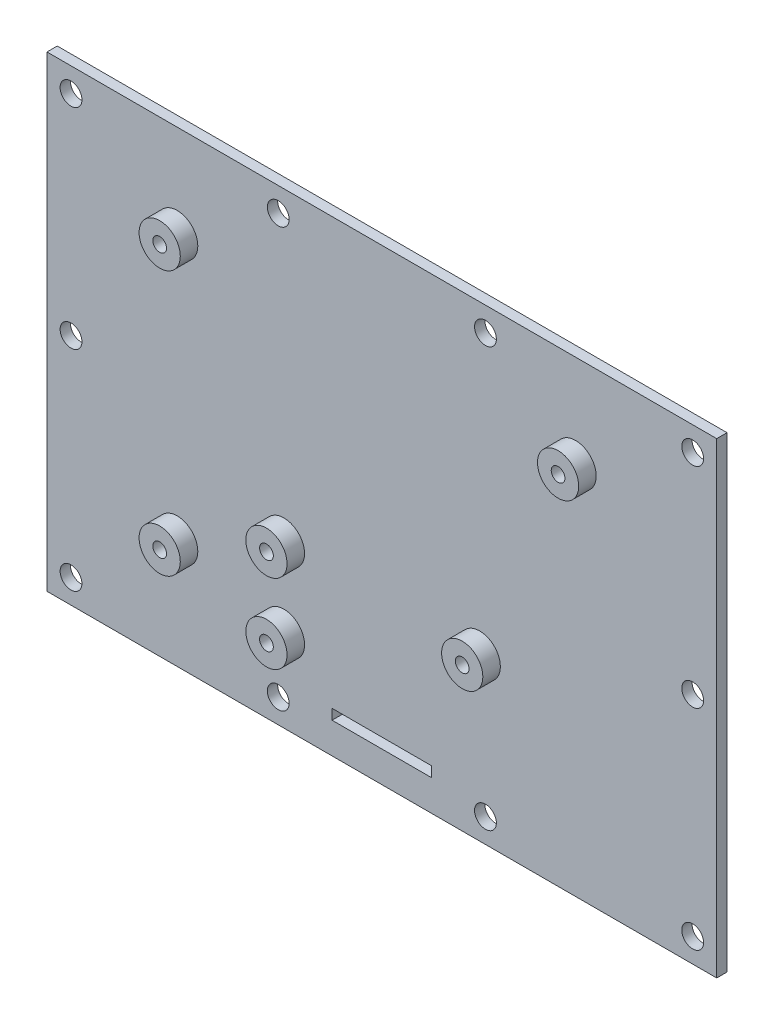
SolidWorks part; units mm, degrees
ref_plane "Front Plane" through (0, 0, 0) normal (0, 0, 1) x (1, 0, 0)
ref_plane "Top Plane" through (0, 0, 0) normal (0, 1, 0) x (1, 0, 0)
ref_plane "Right Plane" through (0, 0, 0) normal (1, 0, 0) x (0, 0, -1)
sketch "Sketch1" plane through (0, 0, 0) normal (0, 0, 1) x (1, 0, 0)
  line L1 (85.5, -56) -> (-85.5, -56)
  line L2 (85.5, -56) -> (85.5, 56)
  line L3 (85.5, 56) -> (-85.5, 56)
  line L4 (-85.5, -56) -> (-85.5, 56)
  line L5 (85.5, -56) -> (-85.5, 56) construction
  line L6 (85.5, 56) -> (-85.5, -56) construction
  line L11 (80, -45) -> (-80, -45)
  line L12 (80, -45) -> (80, 51)
  line L13 (80, 51) -> (-80, 51)
  line L14 (-80, -45) -> (-80, 51)
  line L15 (80, -45) -> (-80, 51) construction
  line L16 (80, 51) -> (-80, -45) construction
  line L17 (-14.5, -56) -> (14.5, -56)
  line L18 (-14.5, -56) -> (-14.5, -59)
  line L19 (-14.5, -59) -> (14.5, -59)
  line L20 (14.5, -56) -> (14.5, -59)
  line L21 (97.5, 68) -> (-97.5, 68)
  line L22 (97.5, 68) -> (97.5, -68)
  line L23 (97.5, -68) -> (-97.5, -68)
  line L24 (-97.5, 68) -> (-97.5, -68)
  line L25 (97.5, 68) -> (-97.5, -68) construction
  line L26 (97.5, -68) -> (-97.5, 68) construction
  point P0 (0, 0)
  point P6 (0, 0)
  point P7 (0, 3)
  point P16 (0, 0)
  dimension "D1" = 171
  dimension "D2" = 112
  dimension "D3" = 96
  dimension "D4" = 160
  dimension "D5" = 5
  dimension "D6" = 71
  dimension "D7" = 29
  dimension "D8" = 3
  dimension "D9" = 12
  dimension "D10" = 17.5
  dimension "D11" = 12
extrude "Boss-Extrude1" add sketch "Sketch1" against normal blind 1.5 contours L4 L1 L2 L3 L11 L14 L13 L12 | L21 L24 L23 L22 L1 L20 L19 L18 L4 L3 L2 | L14 L11 L12 L13 region at (50, -53.9559, 0) region at (0, 3, 0) region at (95.1226, 0, 0)
extrude "Boss-Extrude2" add sketch "Sketch1<3>" along normal blind 1.5 contours L21 L24 L23 L22 L1 L20 L19 L18 L4 L3 L2 | L4 L1 L2 L3 L11 L14 L13 L12 | L14 L11 L12 L13 region at (50, -53.9559, 0) region at (0, 3, 0) region at (95.1226, 0, 0)
sketch "Sketch1<3>" plane through (0, 0, 0) normal (0, 0, 1) x (1, 0, 0) same geometry as "Sketch1"
sketch "Sketch2" plane through (0, 0, 1.5) normal (0, 0, 1) x (1, 0, 0)
  line L0 (97.5, 68) -> (-97.5, 68) construction
  line L1 (90.5, -61) -> (-90.5, -61) construction
  line L2 (90.5, -61) -> (90.5, 61) construction
  line L3 (90.5, 61) -> (-90.5, 61) construction
  line L4 (-90.5, -61) -> (-90.5, 61) construction
  line L5 (90.5, -61) -> (-90.5, 61) construction
  line L6 (90.5, 61) -> (-90.5, -61) construction
  line L7 (-97.5, 68) -> (-97.5, -68) construction
  line L8 (-90.5, 61) -> (-30.1667, 61) construction
  line L9 (-30.1667, 61) -> (30.1667, 61) construction
  line L10 (30.1667, 61) -> (90.5, 61) construction
  circle A0 centre (-90.5, 61) radius 3.175
  circle A2 centre (90.5, 61) radius 3.175
  circle A3 centre (90.5, -61) radius 3.175
  circle A5 centre (-90.5, -61) radius 3.175
  circle A6 centre (-90.5, 0) radius 3.175
  circle A7 centre (30.1667, 61) radius 3.175
  circle A8 centre (90.5, 0) radius 3.175
  circle A9 centre (30.1667, -61) radius 3.175
  circle A10 centre (-30.1667, -61) radius 3.175
  circle A11 centre (-30.1667, 61) radius 3.175
  point P0 (0, 0)
  dimension "D1" = 6.35
  dimension "D2" = 7
  dimension "D3" = 7
extrude "Cut-Extrude1" cut sketch "Sketch2" against normal through all
sketch "Sketch3" plane through (0, 0, 1.5) normal (0, 0, 1) x (1, 0, 0)
  line L0 (-14.5, -59) -> (14.5, -59) construction
  line L1 (28.5, -44) -> (-28.5, -44) construction
  line L2 (28.5, -44) -> (28.5, -21) construction
  line L3 (28.5, -21) -> (-28.5, -21) construction
  line L4 (-28.5, -44) -> (-28.5, -21) construction
  line L5 (28.5, -44) -> (-28.5, -21) construction
  line L6 (28.5, -21) -> (-28.5, -44) construction
  line L11 (-12.1109, -44) -> (11.8889, -44) construction
  line L13 (-12.1109, -44) -> (-12.1109, -40) construction
  line L14 (-12.1109, -40) -> (11.8889, -40) construction
  line L15 (11.8889, -44) -> (11.8889, -40) construction
  line L16 (14.5, -56) -> (-14.5, -56) construction
  circle A0 centre (-28.5, -44) radius 6
  circle A1 centre (-28.5, -44) radius 2
  point P17 (-28.5, -21)
  point P18 (28.5, -21)
  point P21 (0, -56)
  point P22 (0, -44)
  point P23 (0, 0)
  point P24 (0, 0)
  point P25 (0, 0)
  point P26 (0, 0)
  point P27 (0, 0)
  point P28 (0, 0)
  point P29 (0, 0)
  dimension "D1" = 4
  dimension "D2" = 12
  dimension "D3" = 57
  dimension "D4" = 23
  dimension "D5" = 4
  dimension "D6" = 19
extrude "Boss-Extrude3" add sketch "Sketch3" along normal blind 5.1
pattern_sketch "Sketch-Pattern1" of "Boss-Extrude3" driven by "Sketch3"
sketch "Sketch4" plane through (0, 0, 1.5) normal (0, 0, 1) x (1, 0, 0)
  line L0 (-59.586, 40.9925) -> (56.414, 40.9925) construction
  line L1 (-59.586, 40.9925) -> (-59.586, -36.0075) construction
  line L2 (-59.586, -36.0075) -> (56.414, -36.0075) construction
  line L3 (56.414, 40.9925) -> (56.414, -36.0075) construction
  line L4 (-59.586, 40.9925) -> (56.414, -36.0075) construction
  line L5 (-59.586, -36.0075) -> (56.414, 40.9925) construction
  circle A0 centre (-59.586, -36.0075) radius 6
  circle A1 centre (-59.586, -36.0075) radius 2
  circle A2 centre (-28.5, -21) radius 6 construction
  circle A3 centre (-28.5, -21) radius 2 construction
  point P4 (-59.586, 40.9925)
  point P5 (56.414, 40.9925)
  point P7 (-59.586, -36.0075)
  point P14 (0, 0)
  dimension "D1" = 116
  dimension "D2" = 77
extrude "Boss-Extrude6" add sketch "Sketch4" along normal blind 5.1 contours A0 A1 region at (-65.4163, -36.0075, 1.5)
pattern_sketch "Sketch-Pattern2" of "Boss-Extrude6" driven by "Sketch4"
